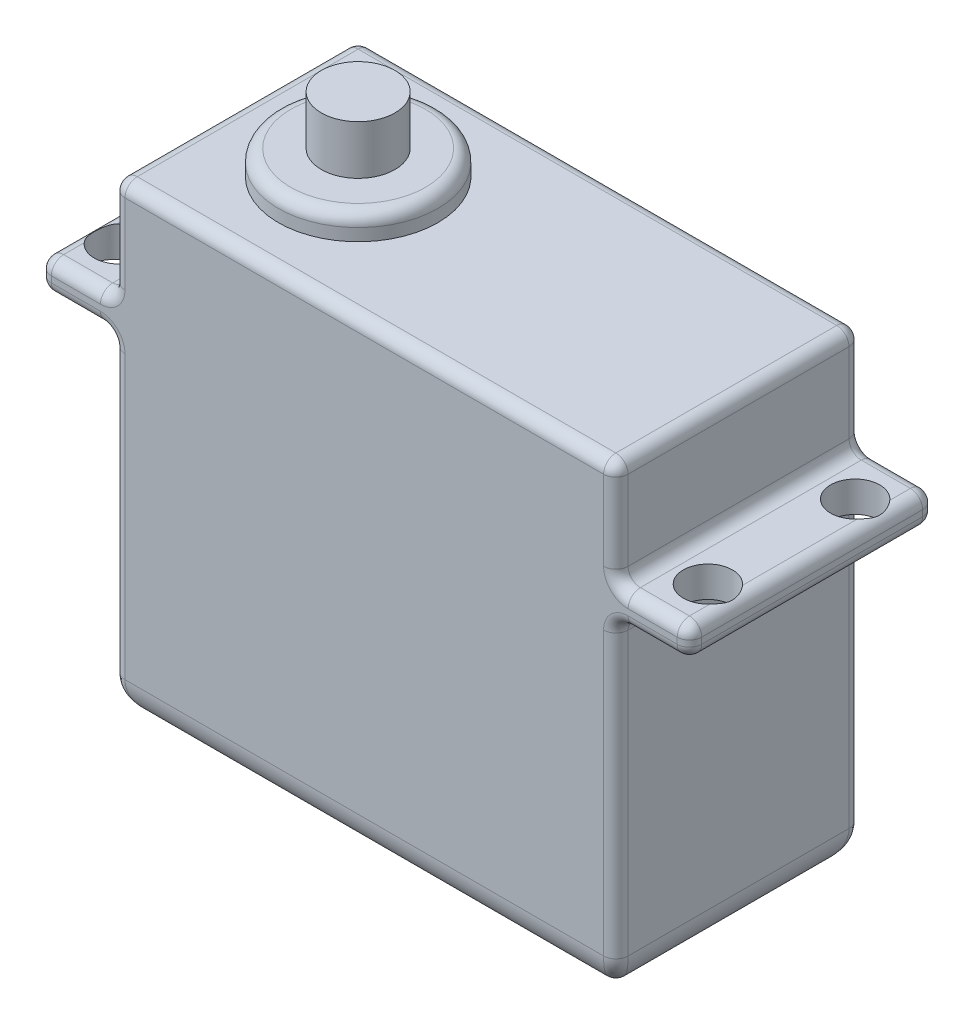
SolidWorks part; units mm, degrees
ref_plane "Front Plane" through (0, 0, 0) normal (0, 0, 1) x (1, 0, 0)
ref_plane "Top Plane" through (0, 0, 0) normal (0, 1, 0) x (1, 0, 0)
ref_plane "Right Plane" through (0, 0, 0) normal (1, 0, 0) x (0, 0, -1)
sketch "Sketch1" plane through (0, 0, 0) normal (0, 0, 1) x (1, 0, 0)
  line L0 (4.0069, 24.6597) -> (10.0069, 24.6597)
  line L1 (-36.9931, 33.1597) -> (4.0069, 33.1597)
  line L2 (-36.9931, 33.1597) -> (-36.9931, 24.6597)
  line L3 (-36.9931, -4.8403) -> (4.0069, -4.8403)
  line L4 (4.0069, 33.1597) -> (4.0069, 24.6597)
  line L5 (-42.9931, 24.6597) -> (-36.9931, 24.6597)
  line L6 (-42.9931, 24.6597) -> (-42.9931, 22.1597)
  line L7 (-42.9931, 22.1597) -> (-36.9931, 22.1597)
  line L8 (10.0069, 24.6597) -> (10.0069, 22.1597)
  line L9 (4.0069, 22.1597) -> (10.0069, 22.1597)
  line L10 (-36.9931, 22.1597) -> (-36.9931, -4.8403)
  line L11 (4.0069, 22.1597) -> (4.0069, -4.8403)
  dimension "D1" = 41
  dimension "D2" = 38
  dimension "D3" = 27
  dimension "D4" = 2.5
  dimension "D5" = 6
  dimension "D6" = 6
extrude "Boss-Extrude1" add sketch "Sketch1" along normal blind 20
sketch "Sketch2" plane through (0, 0, 0) normal (0, 1, 0) x (1, 0, 0)
  line L0 (-42.9931, -10) -> (7.9593, -10) construction
  line L1 (-42.9931, -20) -> (-42.9931, 0) construction
  circle A0 centre (-26.9931, -10) radius 6.5
  dimension "D1" = 13
  dimension "D2" = 10
extrude "Boss-Extrude2" add sketch "Sketch2" along direction (0, -1, 0) on the side of the normal offset from surface (35.1597 mm away) 2 up to face at (-16.4931, 33.1597, 10) offset beyond the face yes
sketch "Sketch3" plane through (0, 0, 0) normal (0, 1, 0) x (1, 0, 0)
  circle A0 centre (-26.9931, -10) radius 3
extrude "Boss-Extrude3" add sketch "Sketch3" along normal offset from surface (39.1597 mm away) 4 up to face at (-20.4931, 35.1597, 10) offset beyond the face yes
sketch "Sketch4" plane through (0, 0, 0) normal (0, 1, 0) x (1, 0, 0)
  line L0 (-40.4931, 5.8605) -> (-40.4931, -26.9525) construction
  line L1 (7.5069, 5.4237) -> (7.5069, -25.5329) construction
  line L2 (-36.9931, -20) -> (-42.9931, -20) construction
  line L3 (10.0069, 0) -> (4.0069, 0) construction
  line L4 (10.0069, -20) -> (4.0069, -20) construction
  line L5 (-36.9931, -20) -> (-36.9931, 0) construction
  circle A0 centre (-40.4931, -4) radius 2
  circle A1 centre (-40.4931, -16) radius 2
  circle A2 centre (7.5069, -4) radius 2
  circle A3 centre (7.5069, -16) radius 2
  dimension "D3" = 4
  dimension "D4" = 4
  dimension "D5" = 4
  dimension "D6" = 4
  dimension "D1" = 2.5
  dimension "D2" = 2.5
  dimension "D7" = 4
  dimension "D8" = 4
  dimension "D9" = 4
  dimension "D10" = 4
extrude "Cut-Extrude1" cut sketch "Sketch4" along normal up to surface (33.1597 mm away) up to face at (-20.4931, 33.1597, 10)
fillet "Fillet1" radius 3 4 edges at (-36.9931, -4.8403, 10) (-16.4931, -4.8403, 20) (4.0069, -4.8403, 10) (-16.4931, -4.8403, 0)
fillet "Fillet2" radius 1 1 edges at (-20.4931, 35.1597, 10)
fillet "Fillet3" radius 1 36 edges at (3.1283, -3.9616, 19.1213) (-36.1144, -3.9616, 19.1213) (-36.1144, -3.9616, 0.8787) (3.1283, -3.9616, 0.8787) (-42.9931, 24.6597, 10) (-42.9931, 22.1597, 10) (10.0069, 22.1597, 10) (10.0069, 24.6597, 10) (-36.9931, 33.1597, 10) (-36.9931, 24.6597, 10) (-36.9931, 22.1597, 10) (4.0069, 22.1597, 10) (4.0069, 24.6597, 10) (4.0069, 33.1597, 10) (-39.9931, 22.1597, 20) (-42.9931, 23.4097, 20) (-39.9931, 24.6597, 20) (-36.9931, 28.9097, 20) (-16.4931, 33.1597, 20) (4.0069, 28.9097, 20) (7.0069, 24.6597, 20) (10.0069, 23.4097, 20) (7.0069, 22.1597, 20) (4.0069, 10.1597, 20) (-36.9931, 10.1597, 20) (7.0069, 22.1597, 0) (10.0069, 23.4097, 0) (7.0069, 24.6597, 0) (4.0069, 28.9097, 0) (-16.4931, 33.1597, 0) (-36.9931, 28.9097, 0) (-39.9931, 24.6597, 0) (-42.9931, 23.4097, 0) (-39.9931, 22.1597, 0) (-36.9931, 10.1597, 0) (4.0069, 10.1597, 0)
